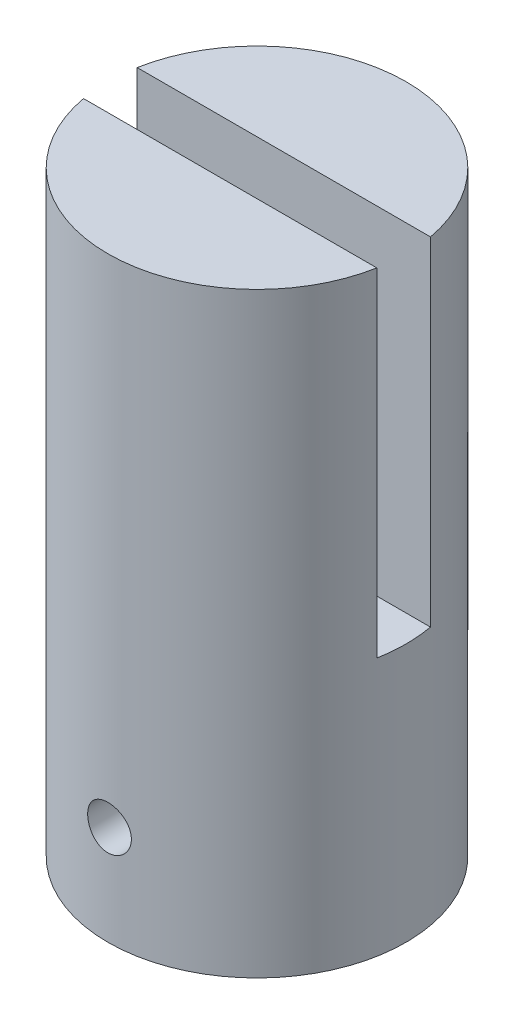
SolidWorks part; units mm, degrees
ref_plane "Front Plane" through (0, 0, 0) normal (0, 0, 1) x (1, 0, 0)
ref_plane "Top Plane" through (0, 0, 0) normal (0, 1, 0) x (1, 0, 0)
ref_plane "Right Plane" through (0, 0, 0) normal (1, 0, 0) x (0, 0, -1)
sketch "Sketch1" plane through (0, 0, 0) normal (0, 1, 0) x (1, 0, 0)
  circle A0 centre (0, 0) radius 3.075
  circle A2 centre (0, 0) radius 7.5
  dimension "D1" = 6.15
  dimension "D3" = 15
extrude "Boss-Extrude1" add sketch "Sketch1" against normal blind 10 contours A0 | A2 region at (-7.2879, 0, 0)
extrude "Boss-Extrude2" add sketch "Sketch1<3>" along normal blind 20 contours A2 | A0 | A0 region at (0, 0, 0) region at (-7.2879, 0, 0)
sketch "Sketch1<3>" plane through (0, 0, 0) normal (0, 1, 0) x (1, 0, 0) same geometry as "Sketch1"
sketch "Sketch2" plane through (0, 20, 0) normal (0, 1, 0) x (1, 0, 0)
  line L0 (-7.3775, 1.35) -> (7.3775, 1.35)
  line L1 (-7.3775, -1.35) -> (7.3775, -1.35)
  circle A0 centre (0, 0) radius 7.5 construction
  arc A1 (-7.3775, 1.35) -> (-7.3775, -1.35) centre (0, 0) ccw
  arc A2 (7.3775, -1.35) -> (7.3775, 1.35) centre (0, 0) ccw
  dimension "D1" = 2.7
  dimension "D2" = 1.35
extrude "Cut-Extrude1" cut sketch "Sketch2" against normal blind 17
sketch "Sketch3" plane through (0, 0, 0) normal (0, 0, 1) x (1, 0, 0)
  circle A0 centre (0, -5) radius 1.1
  dimension "D1" = 2.2
extrude "Cut-Extrude2" cut sketch "Sketch3" against normal through all both and the other way through all
